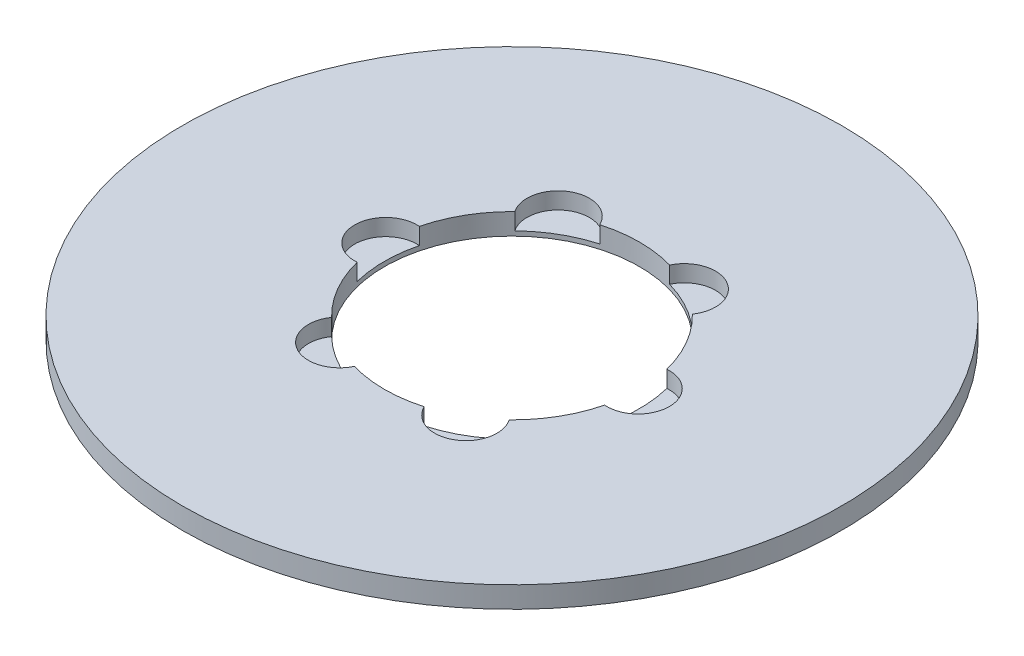
SolidWorks part; units mm, degrees
ref_plane "Front Plane" through (0, 0, 0) normal (0, 0, 1) x (1, 0, 0)
ref_plane "Top Plane" through (0, 0, 0) normal (0, 1, 0) x (1, 0, 0)
ref_plane "Right Plane" through (0, 0, 0) normal (1, 0, 0) x (0, 0, -1)
sketch "Sketch1" plane through (0, 0, 0) normal (0, 1, 0) x (1, 0, 0)
  circle A0 centre (0, 0) radius 77.5
  dimension "FLANGE_OD" = 155
extrude "Boss-Extrude1" add sketch "Sketch1" along normal blind 5
sketch "Sketch2" plane through (0, 0, 0) normal (0, 1, 0) x (1, 0, 0)
  circle A0 centre (0, 0) radius 30
  dimension "BORE_D" = 60
extrude "Cut-Extrude1" cut sketch "Sketch2" along normal through all
sketch "Sketch3" plane through (0, 5, 0) normal (0, 1, 0) x (1, 0, 0)
  circle A0 centre (0, 0) radius 29.6663 construction
  circle A1 centre (-29.6663, 0) radius 7.3353
  dimension "BOLT_D" = 14.6705
  dimension "BOLT_PCD" = 59.3327
extrude "Cut-Extrude2" cut sketch "Sketch3" against normal blind 3.9135
pattern_circular "CirPattern1" count 6 over 360 about axis through (0, 0, 0) along (0, 1, 0) of "Cut-Extrude2"
